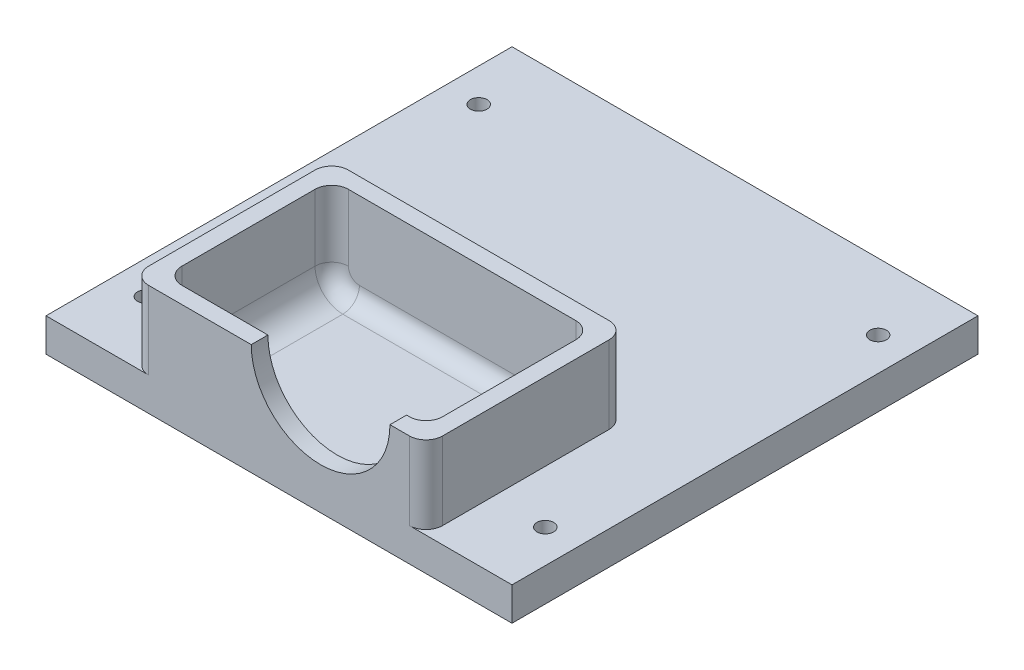
SolidWorks part; units mm, degrees
ref_plane "Front Plane" through (0, 0, 0) normal (0, 0, 1) x (1, 0, 0)
ref_plane "Top Plane" through (0, 0, 0) normal (0, 1, 0) x (1, 0, 0)
ref_plane "Right Plane" through (0, 0, 0) normal (1, 0, 0) x (0, 0, -1)
sketch "Sketch1" plane through (0, 0, 0) normal (0, 1, 0) x (1, 0, 0)
  line L1 (0, 0) -> (84, 0)
  line L2 (0, 0) -> (0, 84)
  line L3 (0, 84) -> (84, 84)
  line L4 (84, 0) -> (84, 84)
  dimension "D1" = 84
  dimension "D2" = 84
extrude "Boss-Extrude1" add sketch "Sketch1" along normal blind 6
sketch "Sketch2" plane through (0, 6, 0) normal (0, 1, 0) x (1, 0, 0)
  line L0 (84, 84) -> (0, 84) construction
  line L1 (0, 84) -> (0, 0) construction
  line L2 (0, 0) -> (84, 0) construction
  line L3 (84, 0) -> (84, 84) construction
  circle A0 centre (6, 72) radius 1.5
  circle A1 centre (6, 12) radius 1.5
  circle A2 centre (78, 12) radius 1.5
  circle A3 centre (78, 72) radius 1.5
  dimension "D1" = 3
  dimension "D2" = 3
  dimension "D3" = 3
  dimension "D4" = 3
  dimension "D6" = 6
  dimension "D7" = 12
  dimension "D8" = 6
  dimension "D9" = 6
  dimension "D10" = 12
  dimension "D11" = 6
  dimension "D5" = 12
  dimension "D12" = 12
extrude "Cut-Extrude1" cut sketch "Sketch2" against normal through all
ref_plane "Plane1" through (0, 0, -42) normal (0, 0, 1) x (1, 0, 0)
sketch "Sketch4" plane through (0, 6, 0) normal (0, 1, 0) x (1, 0, 0)
  line L0 (3, 21) -> (3, 9)
  line L1 (3, 9) -> (13, 9)
  line L2 (13, 15) -> (8, 21)
  line L3 (3, 21) -> (8, 21)
  line L4 (8, 21) -> (13, 15)
  line L5 (13, 15) -> (13, 9)
  line L6 (0, 84) -> (0, 0) construction
  line L7 (0, 0) -> (84, 0) construction
  circle A0 centre (6, 12) radius 1.5
  circle A1 centre (6, 12) radius 1.5 construction
  dimension "D1" = 3
  dimension "D2" = 9
  dimension "D3" = 12
  dimension "D4" = 10
  dimension "D5" = 6
  dimension "D6" = 5
ref_plane "Plane2" through (42, 0, 0) normal (-1, 0, 0) x (0, 0, 1)
sketch "Sketch5" plane through (0, 6, 0) normal (0, 1, 0) x (1, 0, 0)
  line L0 (15.5, 36) -> (15.5, 0)
  line L1 (15.5, 36) -> (68.5, 36)
  line L2 (15.5, 0) -> (68.5, 0)
  line L3 (68.5, 36) -> (68.5, 0)
  line L4 (15.5, 36) -> (68.5, 0) construction
  line L5 (15.5, 0) -> (68.5, 36) construction
  line L6 (42, 3.3) -> (42, -3.3) construction
  line L12 (0, 0) -> (84, 0) construction
  point P1 (42, 18)
  dimension "D1" = 53
  dimension "D2" = 36
extrude "Boss-Extrude2" add sketch "Sketch5" along normal blind 22
sketch "Sketch6" plane through (0, 28, 0) normal (0, 1, 0) x (1, 0, 0)
  line L14 (65.5, 33) -> (18.5, 33)
  line L15 (18.5, 33) -> (18.5, 3)
  line L16 (18.5, 3) -> (65.5, 3)
  line L17 (65.5, 3) -> (65.5, 33)
  line L18 (65.5, 33) -> (18.5, 33)
  line L19 (18.5, 33) -> (18.5, 3)
  line L20 (18.5, 3) -> (65.5, 3)
  line L21 (65.5, 3) -> (65.5, 33)
  dimension "D1" = 3
extrude "Cut-Extrude5" cut sketch "Sketch6" against normal blind 25
fillet "Fillet1" radius 3 10 edges at (65.5, 15.5, -33) (18.5, 15.5, -33) (65.5, 15.5, -3) (18.5, 15.5, -3) (15.5, 17, -36) (68.5, 17, 0) (68.5, 17, -36) (15.5, 17, 0) (42, 3, -3) (42, 3, -33)
fillet "Fillet2" radius 5 6 edges at (19.3787, 3.8787, -3.8787) (19.3787, 3.8787, -32.1213) (64.6213, 3.8787, -32.1213) (64.6213, 3.8787, -3.8787) (65.5, 3, -18) (18.5, 3, -18)
sketch "Sketch8" plane through (0, 0, 0) normal (0, 0, 1) x (1, 0, 0)
  line L0 (84, 6) -> (84, 0) construction
  line L1 (0, 0) -> (84, 0) construction
  circle A0 centre (49.5, 20) radius 12.5
  dimension "D2" = 25
  dimension "D1" = 34.5
  dimension "D3" = 20
extrude "Cut-Extrude6" cut sketch "Sketch8" against normal blind 10
sketch "Sketch9" plane through (0, 0, 0) normal (0, 0, 1) x (1, 0, 0)
  line L0 (0, 0) -> (84, 0) construction
  line L1 (0, 28) -> (84, 28)
  line L2 (0, 28) -> (0, 20)
  line L3 (0, 20) -> (84, 20)
  line L4 (84, 28) -> (84, 20)
  line L5 (84, 6) -> (84, 0) construction
  line L6 (0, 6) -> (0, 0) construction
  line L7 (18.5, 28) -> (39.8953, 28) construction
  dimension "D1" = 20
extrude "Cut-Extrude7" cut sketch "Sketch9" against normal through all both and the other way through all
sketch "Sketch11" plane through (0, 0, 0) normal (0, -1, 0) x (1, 0, 0)
  line L0 (3, -9) -> (13, -9)
  line L1 (13, -9) -> (13, -15)
  line L2 (13, -15) -> (8, -21)
  line L3 (8, -21) -> (3, -21)
  line L4 (3, -21) -> (3, -9)
extrude "Cut-Extrude8" cut sketch "Sketch11" against normal blind 3
mirror "Mirror1" about plane through (0, 0, -42) normal (0, 0, 1) of "Cut-Extrude8" second plane through (42, 0, 0) second plane normal (-1, 0, 0)
